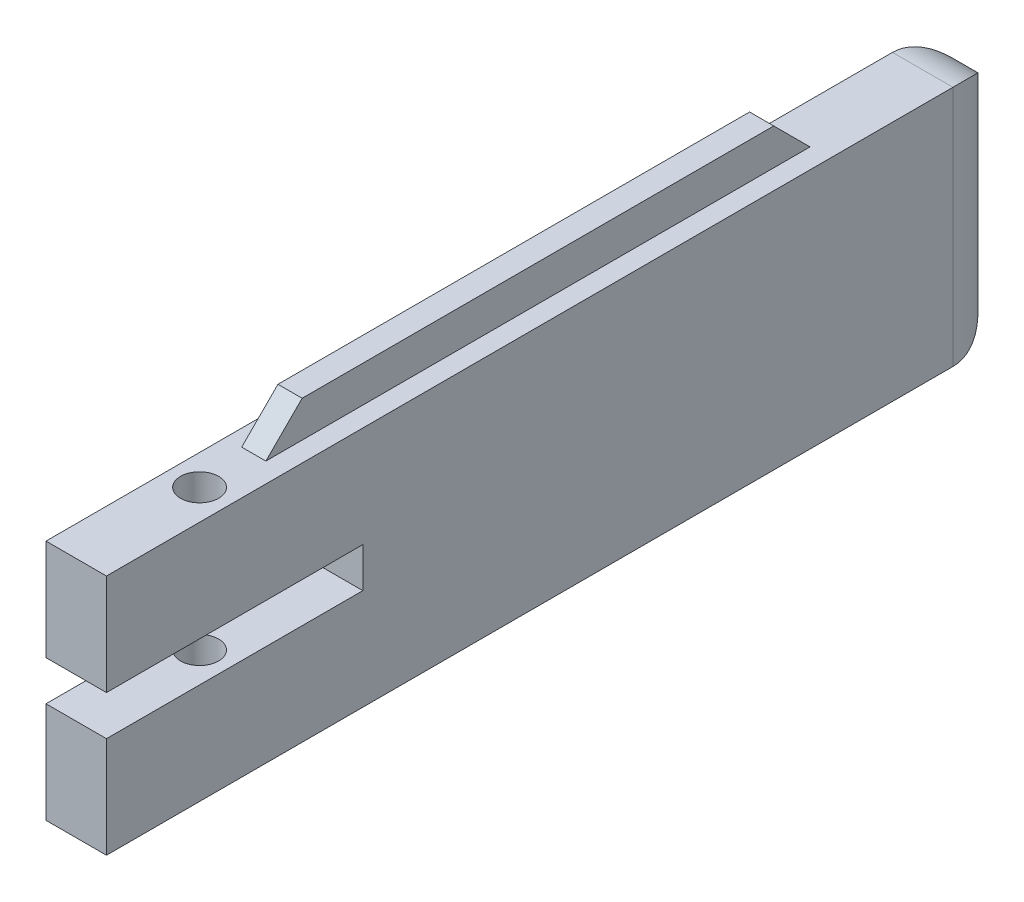
SolidWorks part; units mm, degrees
material "Cast Alloy Steel"
ref_plane "Front Plane" through (0, 0, 0) normal (0, 0, 1) x (1, 0, 0)
ref_plane "Top Plane" through (0, 0, 0) normal (0, 1, 0) x (1, 0, 0)
ref_plane "Right Plane" through (0, 0, 0) normal (1, 0, 0) x (0, 0, -1)
sketch "Sketch1" plane through (0, 0, 0) normal (0, 0, 1) x (1, 0, 0)
  line L0 (-2.5, -20) -> (2.5, -20)
  line L1 (2.5, -20) -> (2.5, 0)
  line L2 (2.5, 0) -> (-2.5, 0)
  line L7 (-2.5, 0) -> (-2.5, -20)
  point P4 (0, 0)
  point P5 (0, -20)
  point P6 (0, 0)
  point P11 (0, 0)
  dimension "D1" = 20
  dimension "D2" = 5
extrude "Boss-Extrude1" add sketch "Sketch1" along normal blind 75
sketch "Sketch6" plane through (2.5, 0, 0) normal (1, 0, 0) x (0, 0, -1)
  line L0 (-75, -8.35) -> (-53.8, -8.35)
  line L1 (-75, -20) -> (-75, 0) construction
  line L2 (-53.8, -8.35) -> (-53.8, -11.65)
  line L3 (-53.8, -11.65) -> (-75, -11.65)
  line L5 (-75, -8.35) -> (-75, -11.65)
  dimension "D1" = 8.35
  dimension "D2" = 21.2
  dimension "D3" = 3.3
extrude "Cut-Extrude5" cut sketch "Sketch6" against normal through all
fillet "Fillet2" radius 5 4 edges at (0, -20, 0) (2.5, -10, 0) (0, 0, 0) (-2.5, -10, 0)
sketch "Sketch9" plane through (0, 0, 0) normal (0, 1, 0) x (1, 0, 0)
  line L0 (-2.5, -53.8) -> (2.5, -53.8)
  line L1 (-2.5, -75) -> (-2.5, -5) construction
  line L2 (2.5, -75) -> (2.5, -5) construction
  line L3 (2.5, -75) -> (-2.5, -75) construction
  circle A0 centre (0, -64.8) radius 1.575
  point P8 (0, -53.8)
  dimension "D2" = 3.15
  dimension "D1" = 21.2
  dimension "D3" = 10.2
extrude "Cut-Extrude7" cut sketch "Sketch9" against normal through all contours A0
sketch "Sketch10" plane through (0, 0, 0) normal (0, 1, 0) x (1, 0, 0)
  line L1 (-1.1388, -60.1794) -> (0.8612, -60.1794)
  line L2 (-1.1388, -60.1794) -> (-1.1388, -15.1794)
  line L3 (-1.1388, -15.1794) -> (0.8612, -15.1794)
  line L4 (0.8612, -60.1794) -> (0.8612, -15.1794)
  line L5 (-1.1388, -60.1794) -> (0.8612, -15.1794) construction
  line L6 (-1.1388, -15.1794) -> (0.8612, -60.1794) construction
  point P0 (-0.1388, -37.6794)
  dimension "D1" = 2
  dimension "D2" = 45
extrude "Boss-Extrude5" add sketch "Sketch10" along normal blind 3
chamfer "Chamfer4" distance 3 angle 45 1 edges at (-0.1388, 3, 60.1794)
chamfer "Chamfer5" distance 3 angle 45 1 edges at (-0.1388, 3, 15.1794)
